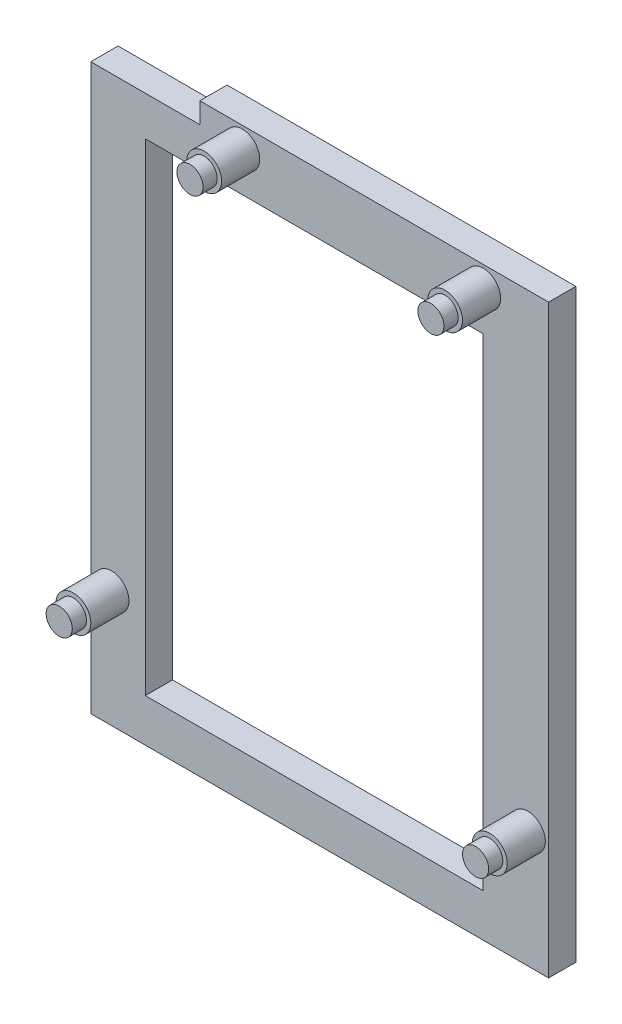
SolidWorks part; units mm, degrees
ref_plane "Front Plane" through (0, 0, 0) normal (0, 0, 1) x (1, 0, 0)
ref_plane "Top Plane" through (0, 0, 0) normal (0, 1, 0) x (1, 0, 0)
ref_plane "Right Plane" through (0, 0, 0) normal (1, 0, 0) x (0, 0, -1)
sketch "Sketch1" plane through (0, 0, 0) normal (0, 0, 1) x (1, 0, 0)
  line L0 (0, 0) -> (53.34, 0)
  line L1 (53.34, 0) -> (53.34, 65.786)
  line L2 (0, 0) -> (0, 65.786)
  line L3 (0, 65.786) -> (12.7, 65.786)
  line L4 (12.7, 65.786) -> (12.7, 68.199)
  line L5 (12.7, 68.199) -> (45.72, 68.199)
  line L6 (45.72, 68.199) -> (53.34, 68.199)
  line L7 (53.34, 68.199) -> (53.34, 65.786)
  line L8 (0, 65.786) -> (17.653, 65.786) construction
  line L9 (53.34, 65.786) -> (45.72, 65.786) construction
  line L10 (53.34, 0) -> (50.927, 0) construction
  line L11 (50.927, 0) -> (50.927, 13.589) construction
  line L13 (12.7, 57.3809) -> (45.72, 57.3809)
  line L14 (12.7, 57.3809) -> (12.7, 4.9965)
  line L15 (12.7, 4.9965) -> (45.72, 4.9965)
  line L16 (45.72, 57.3809) -> (45.72, 4.9965)
  circle A0 centre (17.653, 65.786) radius 1.524
  circle A1 centre (45.72, 65.786) radius 1.524
  circle A2 centre (50.927, 13.589) radius 1.524
  circle A3 centre (2.413, 13.589) radius 1.524
  circle A4 centre (50.927, 13.589) radius 2.032
  circle A5 centre (2.413, 13.589) radius 2.032
  circle A6 centre (17.653, 65.786) radius 2.032
  circle A7 centre (45.72, 65.786) radius 2.032
  dimension "D4" = 2.413
  dimension "D5" = 2.413
  dimension "D1" = 65.786
  dimension "D2" = 65.786
  dimension "D3" = 2.413
extrude "Boss-Extrude1" add sketch "Sketch1" along normal blind 3.175 contours L7 L6 L5 L4 L3 L2 L0 L1 A7 A6 A5 A4 L13 L16 L15 L14 region at (0.8658, 32.893, 0)
extrude "Boss-Extrude2" add sketch "Sketch1<3>" along normal blind 7.62 contours A6 A0 | A7 A1 | A4 A2 | A5 A3 region at (48.9525, 13.589, 0) region at (0.4385, 13.589, 0) region at (15.6785, 65.786, 0) region at (43.7455, 65.786, 0)
sketch "Sketch1<3>" plane through (0, 0, 0) normal (0, 0, 1) x (1, 0, 0) same geometry as "Sketch1"
extrude "Boss-Extrude3" add sketch "Sketch1<4>" along normal blind 9.271 contours A3 | A0 | A1 | A2 region at (17.653, 65.786, 0) region at (45.72, 65.786, 0) region at (50.927, 13.589, 0) region at (2.413, 13.589, 0)
sketch "Sketch1<4>" plane through (0, 0, 0) normal (0, 0, 1) x (1, 0, 0) same geometry as "Sketch1"
sketch "Sketch2" plane through (0, 0, 3.175) normal (0, 0, 1) x (1, 0, 0)
  line L0 (12.7, 4.9965) -> (6.35, 4.9965)
  line L1 (12.7, 57.3809) -> (6.35, 57.3809)
  line L2 (6.35, 4.9965) -> (6.35, 57.3809)
  line L3 (12.7, 4.9965) -> (12.7, 57.3809)
  line L4 (6.35, 57.3809) -> (6.35, 61.1909)
  line L5 (45.72, 57.3809) -> (45.72, 61.1909)
  line L6 (45.72, 61.1909) -> (6.35, 61.1909)
  line M11 (12.7, 57.3809) -> (45.72, 57.3809)
  line M14 (12.7, 4.9965) -> (12.7, 57.3809)
extrude "Cut-Extrude1" cut sketch "Sketch2" against normal blind 9.271 contours L2 L0 L1 M14 | L5 L6 L4 L1 M11 region at (9.525, 31.1887, 3.175) region at (26.035, 59.2859, 3.175)
